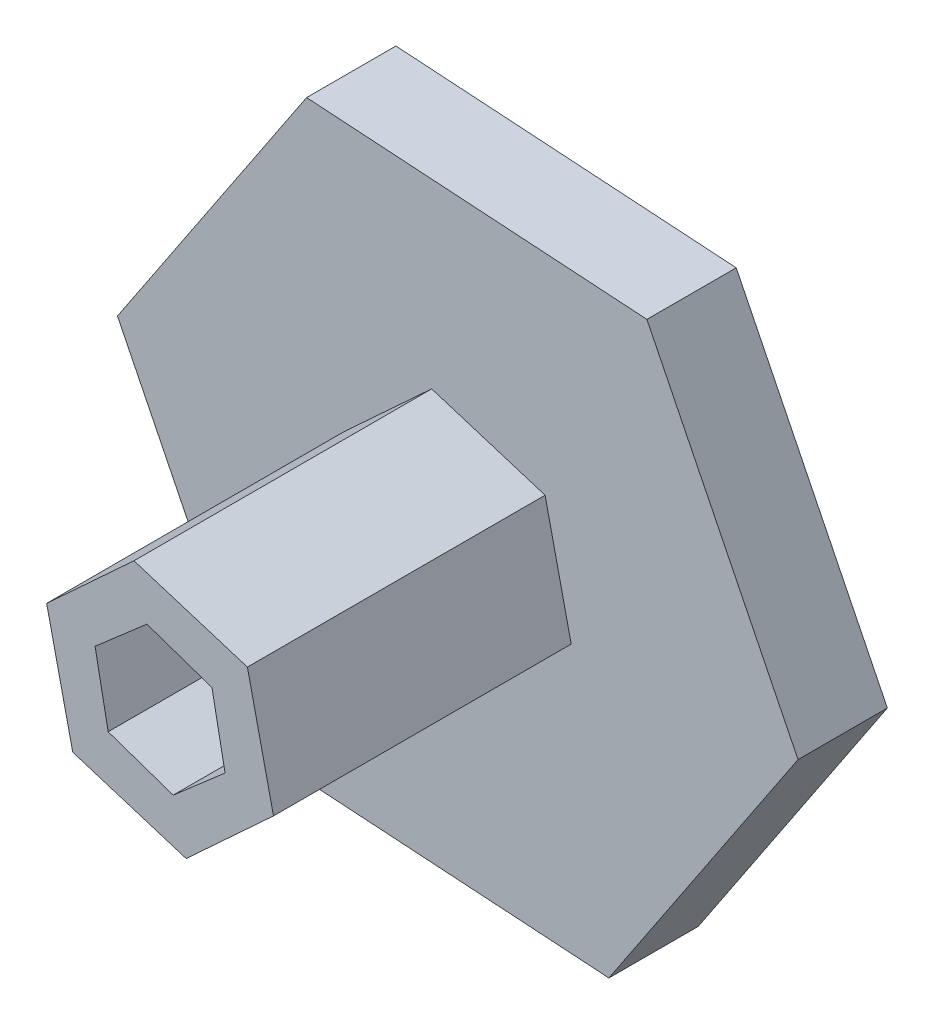
SolidWorks part; units mm, degrees
ref_plane "Front Plane" through (0, 0, 0) normal (0, 0, 1) x (1, 0, 0)
ref_plane "Top Plane" through (0, 0, 0) normal (0, 1, 0) x (1, 0, 0)
ref_plane "Right Plane" through (0, 0, 0) normal (1, 0, 0) x (0, 0, -1)
sketch "Sketch1" plane through (0, 0, 0) normal (0, 0, 1) x (1, 0, 0)
  line L1 (4.428, 3.8473) -> (-1.1179, 5.7584)
  line L2 (-1.1179, 5.7584) -> (-5.5458, 1.9111)
  line L3 (-5.5458, 1.9111) -> (-4.428, -3.8473)
  line L4 (-4.428, -3.8473) -> (1.1179, -5.7584)
  line L5 (1.1179, -5.7584) -> (5.5458, -1.9111)
  line L6 (5.5458, -1.9111) -> (4.428, 3.8473)
  line L7 (16.1391, 24.2086) -> (-12.8957, 26.0812)
  line L8 (-12.8957, 26.0812) -> (-29.0348, 1.8725)
  line L9 (-29.0348, 1.8725) -> (-16.1391, -24.2086)
  line L10 (-16.1391, -24.2086) -> (12.8957, -26.0812)
  line L11 (12.8957, -26.0812) -> (29.0348, -1.8725)
  line L12 (29.0348, -1.8725) -> (16.1391, 24.2086)
  line L13 (7.4513, 6.8723) -> (-2.2259, 9.8892)
  line L14 (-2.2259, 9.8892) -> (-9.6772, 3.0169)
  line L15 (-9.6772, 3.0169) -> (-7.4513, -6.8723)
  line L16 (-7.4513, -6.8723) -> (2.2259, -9.8892)
  line L17 (2.2259, -9.8892) -> (9.6772, -3.0169)
  line L18 (9.6772, -3.0169) -> (7.4513, 6.8723)
  circle A2 centre (0, 0) radius 5.08 construction
  circle A3 centre (0, 0) radius 25.1971 construction
  circle A4 centre (0, 0) radius 8.7785 construction
extrude "Boss-Extrude1" add sketch "Sketch1" against normal blind 7.62 contours L11 L12 L7 L8 L9 L10 L18 L17 L16 L15 L14 L13 region at (21.8872, 10.8221, 0)
extrude "Boss-Extrude2" add sketch "Sketch1<3>" along normal blind 25.4 and the other way blind 7.62 contours L17 L18 L13 L14 L15 L16 L6 L5 L4 L3 L2 L1 region at (8.2943, 1.867, 0)
sketch "Sketch1<3>" plane through (0, 0, 0) normal (0, 0, 1) x (1, 0, 0) same geometry as "Sketch1"
sketch "Sketch2" plane through (0, 0, -7.62) normal (0, 0, -1) x (-1, 0, 0)
  line L1 (1.1179, 5.7584) -> (-4.428, 3.8473)
  line L2 (-4.428, 3.8473) -> (-5.5458, -1.9111)
  line L3 (-5.5458, -1.9111) -> (-1.1179, -5.7584)
  line L4 (-1.1179, -5.7584) -> (4.428, -3.8473)
  line L5 (4.428, -3.8473) -> (5.5458, 1.9111)
  line L6 (5.5458, 1.9111) -> (1.1179, 5.7584)
  circle A0 centre (0, 0) radius 5.08 construction
extrude "Boss-Extrude3" add sketch "Sketch2" against normal blind 7.62
